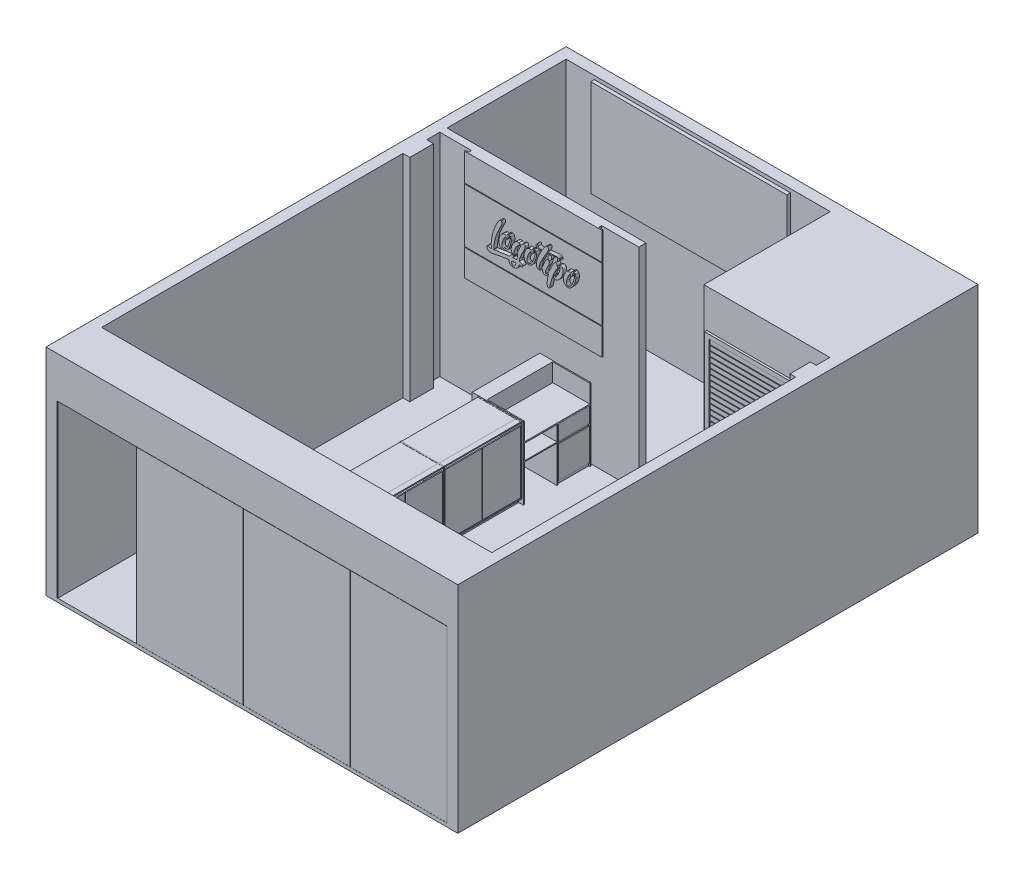
SolidWorks part; units mm, degrees
other "Cámara2"
other "Cámara3"
other "Cámara4"
other "Cámara5"
ref_plane "Alzado" through (0, 0, 0) normal (0, 0, 1) x (1, 0, 0)
ref_plane "Planta" through (0, 0, 0) normal (0, 1, 0) x (1, 0, 0)
ref_plane "Vista lateral" through (0, 0, 0) normal (1, 0, 0) x (0, 0, -1)
sketch "Croquis2" plane through (0, 0, 0) normal (0, 1, 0) x (1, 0, 0)
  line L0 (-7849.2928, -5615.0091) -> (-7999.2928, -5615.0091)
  line L1 (-7849.2928, 1434.9909) -> (-4194.2928, 1434.9909)
  line L2 (-7849.2928, 1434.9909) -> (-7849.2928, -495.0091)
  line L3 (-7849.2928, -825.0091) -> (-7849.2928, -5615.0091)
  line L4 (-2449.2928, -315.0091) -> (-2449.2928, -505.0091)
  line L5 (-2449.2928, -788.0091) -> (-2449.2928, -5615.0091)
  line L7 (-2449.2928, -315.0091) -> (-4194.2928, -315.0091)
  line L8 (-4194.2928, 1434.9909) -> (-4194.2928, -315.0091)
  line L9 (-2449.2928, -505.0091) -> (-2529.2928, -505.0091)
  line L11 (-2449.2928, -788.0091) -> (-2529.2928, -788.0091)
  line L12 (-2529.2928, -505.0091) -> (-2529.2928, -788.0091)
  line L13 (-7849.2928, -495.0091) -> (-7754.2928, -495.0091)
  line L15 (-7849.2928, -825.0091) -> (-7754.2928, -825.0091)
  line L16 (-7754.2928, -495.0091) -> (-7754.2928, -825.0091)
  line L17 (-2299.2928, -5615.0091) -> (-2449.2928, -5615.0091)
  line L18 (-2299.2928, -5615.0091) -> (-2299.2928, 1584.9909)
  line L19 (-2299.2928, 1584.9909) -> (-7999.2928, 1584.9909)
  line L20 (-7999.2928, -5615.0091) -> (-7999.2928, 1584.9909)
  dimension "D3" = 1750
  dimension "D4" = 1745
  dimension "D5" = 190
  dimension "D6" = 283
  dimension "D7" = 80
  dimension "D8" = 1930
  dimension "D9" = 330
  dimension "D10" = 95
  dimension "D11" = 150
  dimension "D12" = 150
  dimension "D13" = 150
extrude "Saliente-Extruir1" add sketch "Croquis2" along normal blind 2930
sketch "Croquis3" plane through (-2449.2928, 0, 0) normal (-1, 0, 0) x (0, 0, 1)
  line L0 (788.0091, 0) -> (5615.0091, 0) construction
  line L1 (5615.0091, 2930) -> (4995.0091, 2930)
  line L2 (5615.0091, 2930) -> (5615.0091, 2360)
  line L3 (5615.0091, 2360) -> (4995.0091, 2360)
  line L4 (4995.0091, 2930) -> (4995.0091, 2360)
  dimension "D1" = 620
  dimension "D2" = 2360
extrude "Saliente-Extruir2" add sketch "Croquis3" along normal blind 5461
sketch "Croquis4" plane through (0, 0, 4995.0091) normal (0, 0, -1) x (-1, 0, 0)
  line L0 (7849.2928, 2930) -> (2449.2928, 2930) construction
  line L1 (7649.2928, 2410) -> (7049.2928, 2410)
  line L2 (7649.2928, 2410) -> (7649.2928, 2830)
  line L3 (7649.2928, 2830) -> (7049.2928, 2830)
  line L4 (7049.2928, 2410) -> (7049.2928, 2830)
  line L5 (7849.2928, 2360) -> (2449.2928, 2360) construction
  line L6 (7849.2928, 2360) -> (7849.2928, 2930) construction
  line L7 (6159.2928, 2410) -> (6159.2928, 2830)
  line L8 (6759.2928, 2830) -> (6159.2928, 2830)
  line L9 (6759.2928, 2410) -> (6759.2928, 2830)
  line L10 (6759.2928, 2410) -> (6159.2928, 2410)
  line L11 (5269.2928, 2410) -> (5269.2928, 2830)
  line L12 (5869.2928, 2830) -> (5269.2928, 2830)
  line L13 (5869.2928, 2410) -> (5869.2928, 2830)
  line L14 (5869.2928, 2410) -> (5269.2928, 2410)
  line L15 (4379.2928, 2410) -> (4379.2928, 2830)
  line L16 (4979.2928, 2830) -> (4379.2928, 2830)
  line L17 (4979.2928, 2410) -> (4979.2928, 2830)
  line L18 (4979.2928, 2410) -> (4379.2928, 2410)
  line L19 (3489.2928, 2410) -> (3489.2928, 2830)
  line L20 (4089.2928, 2830) -> (3489.2928, 2830)
  line L21 (4089.2928, 2410) -> (4089.2928, 2830)
  line L22 (4089.2928, 2410) -> (3489.2928, 2410)
  line L23 (2599.2928, 2410) -> (2599.2928, 2830)
  line L24 (3199.2928, 2830) -> (2599.2928, 2830)
  line L25 (3199.2928, 2410) -> (3199.2928, 2830)
  line L26 (3199.2928, 2410) -> (2599.2928, 2410)
  dimension "D1" = 100
  dimension "D2" = 50
  dimension "D3" = 600
  dimension "D4" = 200
  dimension "D5" = 6
extrude "Cortar-Extruir1" cut sketch "Croquis4" against normal blind 500
sketch "Croquis5" plane through (0, 0, 0) normal (0, -1, 0) x (1, 0, 0)
  line L1 (-2299.2928, -1584.9909) -> (-7999.2928, -1584.9909)
  line L2 (-2299.2928, -1584.9909) -> (-2299.2928, 5615.0091)
  line L3 (-2299.2928, 5615.0091) -> (-7999.2928, 5615.0091)
  line L4 (-7999.2928, -1584.9909) -> (-7999.2928, 5615.0091)
extrude "Saliente-Extruir3" add sketch "Croquis5" along normal blind 50
sketch "Croquis6" plane through (0, 0, -1434.9909) normal (0, 0, 1) x (1, 0, 0)
  line L0 (-7999.2928, 2930) -> (-2299.2928, 2930) construction
  line L1 (-7409.2928, 2930) -> (-4694.2928, 2930)
  line L2 (-7409.2928, 2930) -> (-7409.2928, 1590)
  line L3 (-7409.2928, 1590) -> (-4694.2928, 1590)
  line L4 (-4694.2928, 2930) -> (-4694.2928, 1590)
  line L5 (-7849.2928, 2930) -> (-7849.2928, 0) construction
  line L6 (-7849.2928, 0) -> (-4194.2928, 0) construction
  line L7 (-4194.2928, 2930) -> (-4194.2928, 0) construction
  dimension "D1" = 440
  dimension "D2" = 1590
  dimension "D3" = 500
extrude "Saliente-Extruir4" add sketch "Croquis6" along normal blind 50 from offset 50 separate body
sketch "Croquis7" plane through (0, 0, 0) normal (0, 1, 0) x (1, 0, 0)
  line L0 (-7849.2928, -495.0091) -> (-7849.2928, 1434.9909) construction
  line L1 (-7849.2928, -315.0091) -> (-5094.2928, -315.0091)
  line L2 (-7849.2928, -315.0091) -> (-7849.2928, -215.0091)
  line L3 (-7849.2928, -215.0091) -> (-5094.2928, -215.0091)
  line L4 (-5094.2928, -315.0091) -> (-5094.2928, -215.0091)
  line L5 (-4194.2928, 1434.9909) -> (-4194.2928, -315.0091) construction
  dimension "D1" = 100
  dimension "D2" = 900
extrude "Saliente-Extruir5" add sketch "Croquis7" along normal up to vertex (2930 mm away) up to point (-7849.2928, 2930, 495.0091)
sketch "Croquis8" plane through (0, 0, 5615.0091) normal (0, 0, 1) x (1, 0, 0)
  line L0 (-7849.2928, 2930) -> (-7849.2928, 0) construction
  line L1 (-2451.2979, 1.2463) -> (-6749.2928, 1.2463)
  line L2 (-2451.2979, 1.2463) -> (-2451.2979, 2356.8001)
  line L3 (-2451.2979, 2356.8001) -> (-6749.2928, 2356.8001)
  line L4 (-6749.2928, 1.2463) -> (-6749.2928, 2356.8001)
  dimension "D1" = 1100
extrude "Saliente-Extruir6" add sketch "Croquis8" against normal blind 8 separate body
sketch "Croquis9" plane through (0, 0, 5615.0091) normal (0, 0, 1) x (1, 0, 0)
  line L0 (-2451.2979, 2356.8001) -> (-6749.2928, 2356.8001) construction
  line L1 (-5269.2928, 2356.8001) -> (-5264.2928, 2356.8001)
  line L2 (-5269.2928, 2356.8001) -> (-5269.2928, 0)
  line L3 (-5269.2928, 0) -> (-5264.2928, 0)
  line L4 (-5264.2928, 2356.8001) -> (-5264.2928, 0)
  line L5 (-2449.2928, 0) -> (-7849.2928, 0) construction
  line L6 (-3784.2928, 2356.8001) -> (-3784.2928, 0)
  line L7 (-3789.2928, 2356.8001) -> (-3789.2928, 0)
  line L8 (-3789.2928, 2356.8001) -> (-3784.2928, 2356.8001)
  line L9 (-3789.2928, 0) -> (-3784.2928, 0)
  line L10 (-6749.2928, 2356.8001) -> (-6749.2928, 1.2463) construction
  dimension "D1" = 5
  dimension "D3" = 1480
  dimension "D2" = 2
extrude "Cortar-Extruir2" cut sketch "Croquis9" against normal blind 8
sketch "Croquis11" plane through (0, 0, 0) normal (0, 1, 0) x (1, 0, 0)
  line L1 (-6273.8185, -5586.5744) -> (-5793.8185, -5586.5744)
  line L2 (-6273.8185, -5586.5744) -> (-6273.8185, -353.2208)
  line L3 (-6273.8185, -353.2208) -> (-5793.8185, -353.2208)
  line L4 (-5793.8185, -5586.5744) -> (-5793.8185, -353.2208)
  dimension "D1" = 5233.3536
  dimension "D2" = 480
extrude "Saliente-Extruir7" add sketch "Croquis11" along normal blind 70
sketch "Croquis12" plane through (0, 70, 0) normal (0, 1, 0) x (1, 0, 0)
  line L1 (-5744.5035, -5592.6591) -> (-6344.5035, -5592.6591)
  line L2 (-5744.5035, -5592.6591) -> (-5744.5035, -3442.6591)
  line L3 (-5744.5035, -3442.6591) -> (-6344.5035, -3442.6591)
  line L4 (-6344.5035, -5592.6591) -> (-6344.5035, -3442.6591)
  line L5 (-5744.5035, -3431.128) -> (-6344.5035, -3431.128)
  line L6 (-5744.5035, -3431.128) -> (-5744.5035, -1281.128)
  line L7 (-5744.5035, -1281.128) -> (-6344.5035, -1281.128)
  line L8 (-6344.5035, -3431.128) -> (-6344.5035, -1281.128)
  dimension "D1" = 600
  dimension "D2" = 2150
  dimension "D3" = 2150
extrude "Saliente-Extruir8" add sketch "Croquis12" along normal blind 930
sketch "Croquis13" plane through (0, 1000, 0) normal (0, 1, 0) x (1, 0, 0)
  line L0 (-6344.5035, -1281.128) -> (-6344.5035, -3431.128) construction
  line L1 (-6344.5035, -1296.128) -> (-5731.0709, -1296.128)
  line L2 (-6344.5035, -1296.128) -> (-6344.5035, -3416.128)
  line L3 (-6344.5035, -3416.128) -> (-5731.0709, -3416.128)
  line L4 (-5731.0709, -1296.128) -> (-5731.0709, -3416.128)
  line L5 (-6344.5035, -3442.6591) -> (-6344.5035, -5592.6591) construction
  line L6 (-6344.5035, -3457.6591) -> (-5731.0709, -3457.6591)
  line L7 (-6344.5035, -3457.6591) -> (-6344.5035, -5577.6591)
  line L8 (-6344.5035, -5577.6591) -> (-5731.0709, -5577.6591)
  line L9 (-5731.0709, -3457.6591) -> (-5731.0709, -5577.6591)
  line L10 (-6344.5035, -5592.6591) -> (-5744.5035, -5592.6591) construction
  line L11 (-5744.5035, -3442.6591) -> (-6344.5035, -3442.6591) construction
  line L12 (-6344.5035, -3431.128) -> (-5744.5035, -3431.128) construction
  line L13 (-5744.5035, -1281.128) -> (-6344.5035, -1281.128) construction
  dimension "D1" = 15
  dimension "D2" = 15
  dimension "D3" = 15
  dimension "D4" = 15
extrude "Cortar-Extruir3" cut sketch "Croquis13" against normal blind 915
sketch "Croquis14" plane through (0, 85, 0) normal (0, 1, 0) x (1, 0, 0)
  line L0 (-6344.5035, -1296.128) -> (-6344.5035, -3416.128) construction
  line L1 (-6344.5035, -2356.128) -> (-5744.5035, -2356.128)
  line L2 (-6344.5035, -2356.128) -> (-6344.5035, -2371.128)
  line L3 (-6344.5035, -2371.128) -> (-5744.5035, -2371.128)
  line L4 (-5744.5035, -2356.128) -> (-5744.5035, -2371.128)
  line L5 (-5744.5035, -3416.128) -> (-5744.5035, -1296.128) construction
  line L6 (-6344.5035, -3457.6591) -> (-6344.5035, -5577.6591) construction
  line L7 (-6344.5035, -4517.6591) -> (-5744.5035, -4517.6591)
  line L8 (-6344.5035, -4517.6591) -> (-6344.5035, -4532.6591)
  line L9 (-6344.5035, -4532.6591) -> (-5744.5035, -4532.6591)
  line L10 (-5744.5035, -4517.6591) -> (-5744.5035, -4532.6591)
  line L11 (-5744.5035, -5577.6591) -> (-5744.5035, -3457.6591) construction
  dimension "D1" = 15
  dimension "D2" = 15
extrude "Saliente-Extruir9" add sketch "Croquis14" along normal up to vertex (915 mm away) up to point (-5744.5035, 1000, 3431.128)
sketch "Croquis15" plane through (0, 85, 0) normal (0, 1, 0) x (1, 0, 0)
  line L0 (-5744.5035, -1296.128) -> (-6344.5035, -1296.128) construction
  line L1 (-6335.0437, -1296.128) -> (-6327.0437, -1296.128)
  line L2 (-6335.0437, -1296.128) -> (-6335.0437, -2356.128)
  line L3 (-6335.0437, -2356.128) -> (-6327.0437, -2356.128)
  line L4 (-6327.0437, -1296.128) -> (-6327.0437, -2356.128)
  line L5 (-5744.5035, -2356.128) -> (-6344.5035, -2356.128) construction
  line L6 (-6344.5035, -2371.128) -> (-5744.5035, -2371.128) construction
  line L7 (-6335.0437, -2371.128) -> (-6327.0437, -2371.128)
  line L8 (-6335.0437, -2371.128) -> (-6335.0437, -3416.128)
  line L9 (-6335.0437, -3416.128) -> (-6327.0437, -3416.128)
  line L10 (-6327.0437, -2371.128) -> (-6327.0437, -3416.128)
  line L11 (-6344.5035, -3416.128) -> (-5744.5035, -3416.128) construction
  line L13 (-5744.5035, -3457.6591) -> (-6344.5035, -3457.6591) construction
  line L14 (-6335.0437, -3457.6591) -> (-6327.0437, -3457.6591)
  line L15 (-6335.0437, -3457.6591) -> (-6335.0437, -5577.6591)
  line L16 (-6335.0437, -5577.6591) -> (-6327.0437, -5577.6591)
  line L17 (-6327.0437, -3457.6591) -> (-6327.0437, -5577.6591)
  line L18 (-6344.5035, -5577.6591) -> (-5744.5035, -5577.6591) construction
  dimension "D1" = 8
  dimension "D2" = 8
extrude "Saliente-Extruir10" add sketch "Croquis15" along normal blind 903
sketch "Croquis16" plane through (0, 70, 0) normal (0, 1, 0) x (1, 0, 0)
  line L1 (-6437.669, -341.0207) -> (-5730.993, -341.0207)
  line L2 (-6437.669, -341.0207) -> (-6437.669, -1277.1981)
  line L3 (-6437.669, -1277.1981) -> (-5730.993, -1277.1981)
  line L4 (-5730.993, -341.0207) -> (-5730.993, -1277.1981)
extrude "Saliente-Extruir11" add sketch "Croquis16" along normal up to vertex (930 mm away) and the other way up to vertex (70 mm away) up to point (-5744.5035, 1000, 1281.128) other way up to point (-6273.8185, 0, 353.2208)
sketch "Croquis17" plane through (-6437.669, 0, 0) normal (-1, 0, 0) x (0, 0, 1)
  line L0 (341.0207, 0) -> (1277.1981, 0) construction
  line L1 (1247.1981, 0) -> (371.0207, 0)
  line L2 (1247.1981, 0) -> (1247.1981, 970)
  line L3 (1247.1981, 970) -> (371.0207, 970)
  line L4 (371.0207, 0) -> (371.0207, 970)
  line L5 (341.0207, 1000) -> (1277.1981, 1000) construction
  line L6 (341.0207, 1000) -> (341.0207, 0) construction
  line L7 (1277.1981, 1000) -> (1277.1981, 0) construction
  dimension "D1" = 30
  dimension "D2" = 30
  dimension "D3" = 30
extrude "Cortar-Extruir4" cut sketch "Croquis17" against normal blind 155
sketch "Croquis18" plane through (-6282.669, 0, 0) normal (-1, 0, 0) x (0, 0, 1)
  line L0 (371.0207, 970) -> (371.0207, 0) construction
  line L1 (371.0207, 700.8111) -> (1247.1981, 700.8111)
  line L2 (371.0207, 700.8111) -> (371.0207, 690.8111)
  line L3 (371.0207, 690.8111) -> (1247.1981, 690.8111)
  line L4 (1247.1981, 700.8111) -> (1247.1981, 690.8111)
  line L5 (1247.1981, 0) -> (1247.1981, 970) construction
  line L7 (371.0207, 336.794) -> (1247.1981, 336.794)
  line L8 (371.0207, 336.794) -> (371.0207, 326.794)
  line L9 (371.0207, 326.794) -> (1247.1981, 326.794)
  line L10 (1247.1981, 336.794) -> (1247.1981, 326.794)
  dimension "D1" = 10
  dimension "D2" = 10
extrude "Cortar-Extruir5" cut sketch "Croquis18" against normal blind 155
sketch "Croquis19" plane through (0, 1000, 0) normal (0, 1, 0) x (1, 0, 0)
  line L0 (-5730.993, -1277.1981) -> (-5730.993, -341.0207) construction
  line L1 (-5730.993, -1262.1981) -> (-6244.9145, -1262.1981)
  line L2 (-5730.993, -1262.1981) -> (-5730.993, -356.0207)
  line L3 (-5730.993, -356.0207) -> (-6244.9145, -356.0207)
  line L4 (-6244.9145, -1262.1981) -> (-6244.9145, -356.0207)
  line L5 (-5730.993, -341.0207) -> (-6437.669, -341.0207) construction
  line L6 (-6437.669, -1277.1981) -> (-5730.993, -1277.1981) construction
  dimension "D1" = 15
  dimension "D2" = 15
extrude "Cortar-Extruir6" cut sketch "Croquis19" against normal blind 250
sketch "Croquis20" plane through (-5730.993, 0, 0) normal (1, 0, 0) x (0, 0, -1)
  line L1 (-1262.1981, 0) -> (-356.0207, 0)
  line L2 (-1262.1981, 0) -> (-1262.1981, 474.5874)
  line L3 (-809.1094, 474.5874) -> (-356.0207, 474.5874)
  line L4 (-356.0207, 0) -> (-356.0207, 474.5874)
  line L6 (-1262.1981, 474.5874) -> (-1262.1981, 731.9498)
  line L7 (-1262.1981, 731.9498) -> (-809.1094, 731.9498)
  line L8 (-809.1094, 474.5874) -> (-809.1094, 731.9498)
extrude "Cortar-Extruir7" cut sketch "Croquis20" against normal up to vertex (513.9215 mm away) up to point (-6244.9145, 750, 356.0207)
sketch "Croquis21" plane through (-6244.9145, 0, 0) normal (1, 0, 0) x (0, 0, -1)
  line L0 (-1262.1981, 0) -> (-356.0207, 0) construction
  line L1 (-809.1094, 474.5874) -> (-793.4637, 474.5874)
  line L2 (-809.1094, 474.5874) -> (-809.1094, 0)
  line L3 (-809.1094, 0) -> (-793.4637, 0)
  line L4 (-793.4637, 474.5874) -> (-793.4637, 0)
extrude "Saliente-Extruir12" add sketch "Croquis21" along normal up to vertex (513.9215 mm away) up to point (-5730.993, 474.5874, 356.0207)
sketch "Croquis22" plane through (-5730.993, 0, 0) normal (1, 0, 0) x (0, 0, -1)
  line L0 (-793.4637, 0) -> (-793.4637, 326.794) construction
  line L1 (-793.4637, 0) -> (-356.0207, 0)
  line L2 (-793.4637, 0) -> (-793.4637, 50)
  line L3 (-793.4637, 50) -> (-356.0207, 50)
  line L4 (-356.0207, 0) -> (-356.0207, 50)
  line L5 (-356.0207, 0) -> (-356.0207, 474.5874) construction
  dimension "D1" = 50
extrude "Saliente-Extruir13" add sketch "Croquis22" against normal blind 250 contours L3 L4 L1 L2
sketch "Croquis23" plane through (-5730.993, 0, 0) normal (1, 0, 0) x (0, 0, -1)
  line L1 (-793.4637, 474.5874) -> (-356.0207, 474.5874)
  line L2 (-793.4637, 474.5874) -> (-793.4637, 731.9498)
  line L3 (-793.4637, 731.9498) -> (-356.0207, 731.9498)
  line L4 (-356.0207, 474.5874) -> (-356.0207, 731.9498)
extrude "Cortar-Extruir8" cut sketch "Croquis23" against normal up to vertex (513.9215 mm away) up to point (-6244.9145, 336.794, 809.1094)
sketch "Croquis24" plane through (-5730.993, 0, 0) normal (1, 0, 0) x (0, 0, -1)
  line L0 (-809.1094, 0) -> (-341.0207, 0) construction
  line L1 (-793.4637, 50) -> (-356.0207, 50)
  line L2 (-793.4637, 50) -> (-793.4637, 0)
  line L3 (-793.4637, 0) -> (-356.0207, 0)
  line L4 (-356.0207, 50) -> (-356.0207, 0)
extrude "Cortar-Extruir9" cut sketch "Croquis24" against normal blind 18
sketch "Croquis25" plane through (-5748.993, 0, 0) normal (1, 0, 0) x (0, 0, -1)
  line L1 (-789.5623, 727.895) -> (-358.8959, 727.895)
  line L2 (-789.5623, 727.895) -> (-789.5623, 517.895)
  line L3 (-789.5623, 517.895) -> (-358.8959, 517.895)
  line L4 (-358.8959, 727.895) -> (-358.8959, 517.895)
  line L5 (-789.5623, 487.895) -> (-358.8959, 487.895)
  line L6 (-789.5623, 487.895) -> (-789.5623, 44.4055)
  line L7 (-789.5623, 44.4055) -> (-358.8959, 44.4055)
  line L8 (-358.8959, 487.895) -> (-358.8959, 44.4055)
  dimension "D1" = 210
  dimension "D2" = 30
extrude "Saliente-Extruir14" add sketch "Croquis25" against normal blind 98 and the other way blind 15
sketch "Croquis26" plane through (0, 0, 356.0207) normal (0, 0, 1) x (1, 0, 0)
  line L1 (-5790.7456, 525.0553) -> (-5748.3073, 525.0553)
  line L2 (-5790.7456, 525.0553) -> (-5790.7456, 485.704)
  line L3 (-5790.7456, 485.704) -> (-5748.3073, 485.704)
  line L4 (-5748.3073, 525.0553) -> (-5748.3073, 485.704)
extrude "Saliente-Extruir15" add sketch "Croquis26" along normal up to vertex (437.4431 mm away) up to point (-5730.993, 0, 793.4637)
sketch "Croquis27" plane through (-6244.9145, 0, 0) normal (1, 0, 0) x (0, 0, -1)
  line L0 (-1262.1981, 731.9498) -> (-1262.1981, 0) construction
  line L1 (-1262.1981, 522.4472) -> (-809.1094, 522.4472)
  line L2 (-1262.1981, 522.4472) -> (-1262.1981, 508.8133)
  line L3 (-1262.1981, 508.8133) -> (-809.1094, 508.8133)
  line L4 (-809.1094, 522.4472) -> (-809.1094, 508.8133)
  line L5 (-809.1094, 0) -> (-809.1094, 731.9498) construction
extrude "Saliente-Extruir16" add sketch "Croquis27" along normal up to vertex (513.9215 mm away) up to point (-5730.993, 0, 809.1094)
sketch "Croquis28" plane through (0, 0, 1296.128) normal (0, 0, 1) x (1, 0, 0)
  line L0 (-5744.5035, 1000) -> (-6344.5035, 1000) construction
  line L1 (-6319.4645, 700) -> (-5819.4645, 700)
  line L2 (-6319.4645, 700) -> (-6319.4645, 692)
  line L3 (-6319.4645, 692) -> (-5819.4645, 692)
  line L4 (-5819.4645, 700) -> (-5819.4645, 692)
  line L5 (-6319.4645, 392) -> (-5819.4645, 392)
  line L6 (-6319.4645, 400) -> (-5819.4645, 400)
  line L7 (-5819.4645, 400) -> (-5819.4645, 392)
  line L8 (-6319.4645, 400) -> (-6319.4645, 392)
  dimension "D1" = 500
  dimension "D2" = 8
  dimension "D3" = 300
  dimension "D4" = 2
extrude "Saliente-Extruir17" add sketch "Croquis28" along normal up to vertex (4281.531 mm away) up to point (-5744.5035, 1000, 5577.6591)
sketch "Croquis29" plane through (0, 0, 1296.128) normal (0, 0, 1) x (1, 0, 0)
  line L1 (-6340.7874, 997.831) -> (-5819.4645, 997.831)
  line L2 (-6340.7874, 997.831) -> (-6340.7874, 991.8705)
  line L3 (-6340.7874, 991.8705) -> (-5819.4645, 991.8705)
  line L4 (-5819.4645, 997.831) -> (-5819.4645, 991.8705)
extrude "Saliente-Extruir18" add sketch "Croquis29" along normal up to vertex (4296.531 mm away) up to point (-5744.5035, 1000, 5592.6591)
sketch "Croquis30" plane through (0, 0, 1296.128) normal (0, 0, 1) x (1, 0, 0)
  line L1 (-5818.52, 999.2539) -> (-5745.3813, 999.2539)
  line L2 (-5818.52, 999.2539) -> (-5818.52, 984.2539)
  line L3 (-5818.52, 984.2539) -> (-5745.3813, 984.2539)
  line L4 (-5745.3813, 999.2539) -> (-5745.3813, 984.2539)
  dimension "D1" = 15
extrude "Saliente-Extruir19" add sketch "Croquis30" along normal up to vertex (4281.531 mm away) up to point (-5744.5035, 1000, 5577.6591)
sketch "Croquis31" plane through (-5745.3813, 0, 0) normal (1, 0, 0) x (0, 0, -1)
  line L1 (-1300.1778, 949.2539) -> (-1829.1279, 949.2539)
  line L2 (-1300.1778, 949.2539) -> (-1300.1778, 90.4957)
  line L3 (-1300.1778, 90.4957) -> (-1829.1279, 90.4957)
  line L4 (-1829.1279, 949.2539) -> (-1829.1279, 90.4957)
  line L5 (-1834.8931, 90.4957) -> (-2346.9744, 90.4957)
  line L6 (-1834.8931, 90.4957) -> (-1834.8931, 949.2539)
  line L7 (-1834.8931, 949.2539) -> (-2346.9744, 949.2539)
  line L8 (-2346.9744, 90.4957) -> (-2346.9744, 949.2539)
  line L9 (-2356.128, 984.2539) -> (-1296.128, 984.2539) construction
  line L11 (-2379.7979, 949.2539) -> (-2893.6595, 949.2539)
  line L12 (-2379.7979, 949.2539) -> (-2379.7979, 90.4957)
  line L13 (-2379.7979, 90.4957) -> (-2893.6595, 90.4957)
  line L14 (-2893.6595, 949.2539) -> (-2893.6595, 90.4957)
  line L15 (-3407.9198, 949.2539) -> (-2899.0939, 949.2539)
  line L16 (-3407.9198, 949.2539) -> (-3407.9198, 90.4957)
  line L17 (-3407.9198, 90.4957) -> (-2899.0939, 90.4957)
  line L18 (-2899.0939, 949.2539) -> (-2899.0939, 90.4957)
  line L19 (-3462.3431, 949.2539) -> (-3982.1373, 949.2539)
  line L20 (-3462.3431, 949.2539) -> (-3462.3431, 90.4957)
  line L21 (-3462.3431, 90.4957) -> (-3982.1373, 90.4957)
  line L22 (-3982.1373, 949.2539) -> (-3982.1373, 90.4957)
  line L23 (-4511.3504, 949.3027) -> (-3992.1437, 949.3027)
  line L24 (-4511.3504, 949.3027) -> (-4511.3504, 90.4957)
  line L25 (-4511.3504, 90.4957) -> (-3992.1437, 90.4957)
  line L26 (-3992.1437, 949.3027) -> (-3992.1437, 90.4957)
  line L27 (-4537.0525, 949.3027) -> (-5054.5119, 949.3027)
  line L28 (-4537.0525, 949.3027) -> (-4537.0525, 90.4957)
  line L29 (-4537.0525, 90.4957) -> (-5054.5119, 90.4957)
  line L30 (-5054.5119, 949.3027) -> (-5054.5119, 90.4957)
  line L31 (-5573.1853, 949.3027) -> (-5058.2175, 949.3027)
  line L32 (-5573.1853, 949.3027) -> (-5573.1853, 90.4957)
  line L33 (-5573.1853, 90.4957) -> (-5058.2175, 90.4957)
  line L34 (-5058.2175, 949.3027) -> (-5058.2175, 90.4957)
  dimension "D1" = 35
  dimension "D2" = 35
extrude "Saliente-Extruir20" add sketch "Croquis31" against normal blind 15 separate body
sketch "Croquis32" plane through (0, 0, 0) normal (0, 1, 0) x (1, 0, 0)
  line L0 (-2449.2928, -5615.0091) -> (-7849.2928, -5615.0091) construction
  line L5 (-5362.7687, -4128.084) -> (-2962.7687, -4128.084)
  line L6 (-5362.7687, -4128.084) -> (-5362.7687, -4628.084)
  line L7 (-5362.7687, -4628.084) -> (-2962.7687, -4628.084)
  line L8 (-2962.7687, -4128.084) -> (-2962.7687, -4628.084)
  dimension "D1" = 1486.9252
  dimension "D2" = 2400
  dimension "D3" = 500
extrude "Saliente-Extruir21" add sketch "Croquis32" along normal blind 700
sketch "Croquis33" plane through (0, 0, 4628.084) normal (0, 0, 1) x (1, 0, 0)
  line L12 (-5320.7687, 42) -> (-3004.7687, 42)
  line L13 (-3004.7687, 42) -> (-3004.7687, 658)
  line L14 (-3004.7687, 658) -> (-5320.7687, 658)
  line L15 (-5320.7687, 658) -> (-5320.7687, 42)
  line L16 (-5320.7687, 42) -> (-3004.7687, 42)
  line L17 (-3004.7687, 42) -> (-3004.7687, 658)
  line L18 (-3004.7687, 658) -> (-5320.7687, 658)
  line L19 (-5320.7687, 658) -> (-5320.7687, 42)
  dimension "D1" = 42
extrude "Cortar-Extruir11" cut sketch "Croquis33" against normal up to vertex (500 mm away) up to point (-2962.7687, 700, 4128.084)
sketch "Croquis34" plane through (-5362.7687, 0, 0) normal (-1, 0, 0) x (0, 0, 1)
  line L8 (4170.084, 42) -> (4586.084, 42)
  line L9 (4586.084, 42) -> (4586.084, 658)
  line L10 (4586.084, 658) -> (4170.084, 658)
  line L11 (4170.084, 658) -> (4170.084, 42)
  line L12 (4170.084, 42) -> (4586.084, 42)
  line L13 (4586.084, 42) -> (4586.084, 658)
  line L14 (4586.084, 658) -> (4170.084, 658)
  line L15 (4170.084, 658) -> (4170.084, 42)
  dimension "D1" = 42
extrude "Cortar-Extruir12" cut sketch "Croquis34" against normal up to vertex (2400 mm away) up to point (-2962.7687, 700, 4128.084)
sketch "Croquis35" plane through (0, 42, 0) normal (0, 1, 0) x (1, 0, 0)
  line L1 (-3004.7687, -4586.084) -> (-5320.7687, -4586.084)
  line L2 (-3004.7687, -4586.084) -> (-3004.7687, -4170.084)
  line L3 (-3004.7687, -4170.084) -> (-5320.7687, -4170.084)
  line L4 (-5320.7687, -4586.084) -> (-5320.7687, -4170.084)
extrude "Cortar-Extruir13" cut sketch "Croquis35" against normal up to vertex (42 mm away) up to point (-5362.7687, 0, 4128.084)
sketch "Croquis36" plane through (0, 0, 4628.084) normal (0, 0, 1) x (1, 0, 0)
  line L0 (-5362.7687, 0) -> (-2962.7687, 0) construction
  line L1 (-3004.7687, 42) -> (-5320.7687, 42)
  line L2 (-3004.7687, 42) -> (-3004.7687, 0)
  line L3 (-3004.7687, 0) -> (-5320.7687, 0)
  line L4 (-5320.7687, 42) -> (-5320.7687, 0)
extrude "Cortar-Extruir14" cut sketch "Croquis36" against normal up to vertex (500 mm away) up to point (-3004.7687, 42, 4128.084)
sketch "Croquis37" plane through (0, 0, 4628.084) normal (0, 0, 1) x (1, 0, 0)
  line L0 (-4194.2928, 0) -> (-2449.2928, 0) construction
  line L1 (-4478.7472, 639.7339) -> (-3678.7472, 639.7339)
  line L2 (-4478.7472, 639.7339) -> (-4478.7472, 0)
  line L3 (-4478.7472, 0) -> (-3678.7472, 0)
  line L4 (-3678.7472, 639.7339) -> (-3678.7472, 0)
  dimension "D1" = 800
extrude "Saliente-Extruir22" add sketch "Croquis37" against normal blind 251 and the other way blind 180
sketch "Croquis38" plane through (0, 0, 4808.084) normal (0, 0, 1) x (1, 0, 0)
  line L1 (-4459.2142, 644.1817) -> (-3697.0645, 644.1817)
  line L2 (-4459.2142, 644.1817) -> (-4459.2142, 16.2765)
  line L3 (-4459.2142, 16.2765) -> (-3697.0645, 16.2765)
  line L4 (-3697.0645, 644.1817) -> (-3697.0645, 16.2765)
extrude "Cortar-Extruir15" cut sketch "Croquis38" against normal up to vertex (431 mm away) up to point (-3678.7472, 0, 4377.084)
sketch "Croquis39" plane through (0, 0, 4808.084) normal (0, 0, 1) x (1, 0, 0)
  line L1 (-4450.9926, 447.2858) -> (-3701.879, 447.2858)
  line L2 (-4450.9926, 447.2858) -> (-4450.9926, 439.2858)
  line L3 (-4450.9926, 439.2858) -> (-3701.879, 439.2858)
  line L4 (-3701.879, 447.2858) -> (-3701.879, 439.2858)
  line L5 (-4450.9926, 210.0986) -> (-3701.879, 210.0986)
  line L6 (-4450.9926, 210.0986) -> (-4450.9926, 202.0986)
  line L7 (-4450.9926, 202.0986) -> (-3701.879, 202.0986)
  line L8 (-3701.879, 210.0986) -> (-3701.879, 202.0986)
  dimension "D1" = 8
  dimension "D2" = 8
extrude "Saliente-Extruir23" add sketch "Croquis39" against normal up to vertex (431 mm away) separate body up to point (-4459.2142, 16.2765, 4377.084)
sketch "Croquis40" plane through (0, 0, 4628.084) normal (0, 0, 1) x (1, 0, 0)
  line L1 (-5362.0375, 701.643) -> (-2963.2437, 701.643)
  line L2 (-5362.0375, 701.643) -> (-5362.0375, 831.643)
  line L3 (-5362.0375, 831.643) -> (-2963.2437, 831.643)
  line L4 (-2963.2437, 701.643) -> (-2963.2437, 831.643)
  dimension "D1" = 130
extrude "Saliente-Extruir24" add sketch "Croquis40" against normal up to vertex (500 mm away) separate body up to point (-2962.7687, 700, 4128.084)
sketch "Croquis41" plane through (0, 0, 4628.084) normal (0, 0, 1) x (1, 0, 0)
  line L0 (-2963.2437, 831.643) -> (-5362.0375, 831.643) construction
  line L1 (-5347.0375, 831.643) -> (-2978.2437, 831.643)
  line L2 (-5347.0375, 831.643) -> (-5347.0375, 716.0432)
  line L3 (-5347.0375, 716.0432) -> (-2978.2437, 716.0432)
  line L4 (-2978.2437, 831.643) -> (-2978.2437, 716.0432)
  line L5 (-2963.2437, 701.643) -> (-2963.2437, 831.643) construction
  line L6 (-5362.0375, 831.643) -> (-5362.0375, 701.643) construction
  dimension "D1" = 15
  dimension "D2" = 15
extrude "Cortar-Extruir16" cut sketch "Croquis41" against normal blind 485
sketch "Croquis42" plane through (-2449.2928, 0, 0) normal (-1, 0, 0) x (0, 0, 1)
  line L0 (788.0091, 2930) -> (788.0091, 0) construction
  line L1 (1788.0091, 2401.1932) -> (788.0091, 2401.1932)
  line L2 (1788.0091, 2401.1932) -> (1788.0091, 1.1932)
  line L3 (1788.0091, 1.1932) -> (788.0091, 1.1932)
  line L4 (788.0091, 2401.1932) -> (788.0091, 1.1932)
  line L5 (2818.0091, 2401.1932) -> (2818.0091, 1.1932)
  line L6 (2818.0091, 2401.1932) -> (1818.0091, 2401.1932)
  line L7 (1818.0091, 2401.1932) -> (1818.0091, 1.1932)
  line L8 (2818.0091, 1.1932) -> (1818.0091, 1.1932)
  line L9 (3848.0091, 2401.1932) -> (3848.0091, 1.1932)
  line L10 (3848.0091, 2401.1932) -> (2848.0091, 2401.1932)
  line L11 (2848.0091, 2401.1932) -> (2848.0091, 1.1932)
  line L12 (3848.0091, 1.1932) -> (2848.0091, 1.1932)
  line L13 (4878.0091, 2401.1932) -> (4878.0091, 1.1932)
  line L14 (4878.0091, 2401.1932) -> (3878.0091, 2401.1932)
  line L15 (3878.0091, 2401.1932) -> (3878.0091, 1.1932)
  line L16 (4878.0091, 1.1932) -> (3878.0091, 1.1932)
  dimension "D1" = 1000
  dimension "D2" = 2400
  dimension "D3" = 4
extrude "Saliente-Extruir25" add sketch "Croquis42" along normal blind 15
sketch "Croquis43" plane through (-2464.2928, 0, 0) normal (-1, 0, 0) x (0, 0, 1)
  line L8 (4878.0091, 2401.1932) -> (3878.0091, 2401.1932)
  line L9 (3878.0091, 2401.1932) -> (3878.0091, 1.1932)
  line L10 (3878.0091, 1.1932) -> (4878.0091, 1.1932)
  line L11 (4878.0091, 1.1932) -> (4878.0091, 2401.1932)
  line L12 (4878.0091, 2401.1932) -> (3878.0091, 2401.1932)
  line L13 (3878.0091, 2401.1932) -> (3878.0091, 1.1932)
  line L14 (3878.0091, 1.1932) -> (4878.0091, 1.1932)
  line L15 (4878.0091, 1.1932) -> (4878.0091, 2401.1932)
  line L20 (2818.0091, 2401.1932) -> (1818.0091, 2401.1932)
  line L21 (1818.0091, 2401.1932) -> (1818.0091, 1.1932)
  line L22 (1818.0091, 1.1932) -> (2818.0091, 1.1932)
  line L23 (2818.0091, 1.1932) -> (2818.0091, 2401.1932)
  line L24 (2818.0091, 2401.1932) -> (1818.0091, 2401.1932)
  line L25 (1818.0091, 2401.1932) -> (1818.0091, 1.1932)
  line L26 (1818.0091, 1.1932) -> (2818.0091, 1.1932)
  line L27 (2818.0091, 1.1932) -> (2818.0091, 2401.1932)
  dimension "D1" = 0
  dimension "D2" = 0
extrude "Saliente-Extruir26" add sketch "Croquis43" along normal blind 365
sketch "Croquis44" plane through (-2829.2928, 0, 0) normal (-1, 0, 0) x (0, 0, 1)
  line L8 (4863.0091, 16.1932) -> (4863.0091, 2386.1932)
  line L9 (4863.0091, 2386.1932) -> (3893.0091, 2386.1932)
  line L10 (3893.0091, 2386.1932) -> (3893.0091, 16.1932)
  line L11 (3893.0091, 16.1932) -> (4863.0091, 16.1932)
  line L12 (4863.0091, 16.1932) -> (4863.0091, 2386.1932)
  line L13 (4863.0091, 2386.1932) -> (3893.0091, 2386.1932)
  line L14 (3893.0091, 2386.1932) -> (3893.0091, 16.1932)
  line L15 (3893.0091, 16.1932) -> (4863.0091, 16.1932)
  line L20 (2803.0091, 16.1932) -> (2803.0091, 2386.1932)
  line L21 (2803.0091, 2386.1932) -> (1833.0091, 2386.1932)
  line L22 (1833.0091, 2386.1932) -> (1833.0091, 16.1932)
  line L23 (1833.0091, 16.1932) -> (2803.0091, 16.1932)
  line L24 (2803.0091, 16.1932) -> (2803.0091, 2386.1932)
  line L25 (2803.0091, 2386.1932) -> (1833.0091, 2386.1932)
  line L26 (1833.0091, 2386.1932) -> (1833.0091, 16.1932)
  line L27 (1833.0091, 16.1932) -> (2803.0091, 16.1932)
  dimension "D1" = 15
  dimension "D2" = 15
extrude "Cortar-Extruir17" cut sketch "Croquis44" against normal up to vertex (380 mm away) up to point (-2449.2928, 2401.1932, 2818.0091)
sketch "Croquis45" plane through (-2449.2928, 0, 0) normal (-1, 0, 0) x (0, 0, 1)
  line L1 (4856.4501, 21.7147) -> (3896.8183, 21.7147)
  line L2 (4856.4501, 21.7147) -> (4856.4501, 371.7147)
  line L3 (4856.4501, 371.7147) -> (3896.8183, 371.7147)
  line L4 (3896.8183, 21.7147) -> (3896.8183, 371.7147)
  line L5 (2799.3583, 21.7147) -> (1836.9807, 21.7147)
  line L6 (2799.3583, 21.7147) -> (2799.3583, 371.7147)
  line L7 (2799.3583, 371.7147) -> (1836.9807, 371.7147)
  line L8 (1836.9807, 21.7147) -> (1836.9807, 371.7147)
  dimension "D1" = 350
  dimension "D2" = 350
extrude "Saliente-Extruir27" add sketch "Croquis45" along normal blind 365
sketch "Croquis46" plane through (-2814.2928, 0, 0) normal (-1, 0, 0) x (0, 0, 1)
  line L0 (1836.9807, 21.7147) -> (2799.3583, 21.7147) construction
  line L1 (1836.9807, 375.1203) -> (2318.1695, 375.1203)
  line L2 (1836.9807, 375.1203) -> (1836.9807, 21.7147)
  line L3 (1836.9807, 21.7147) -> (2318.1695, 21.7147)
  line L4 (2318.1695, 375.1203) -> (2318.1695, 21.7147)
  line L5 (3896.8183, 21.7147) -> (4856.4501, 21.7147) construction
  line L6 (2323.1695, 375.1203) -> (2799.3583, 375.1203)
  line L7 (2323.1695, 375.1203) -> (2323.1695, 21.7147)
  line L8 (2323.1695, 21.7147) -> (2799.3583, 21.7147)
  line L9 (2799.3583, 375.1203) -> (2799.3583, 21.7147)
  line L10 (3896.6897, 375.1203) -> (4376.6342, 375.1203)
  line L11 (3896.6897, 375.1203) -> (3896.6897, 21.7147)
  line L12 (3896.6897, 21.7147) -> (4376.6342, 21.7147)
  line L13 (4376.6342, 375.1203) -> (4376.6342, 21.7147)
  line L15 (4381.6342, 375.1203) -> (4856.4501, 375.1203)
  line L16 (4381.6342, 375.1203) -> (4381.6342, 21.7147)
  line L17 (4381.6342, 21.7147) -> (4856.4501, 21.7147)
  line L18 (4856.4501, 375.1203) -> (4856.4501, 21.7147)
  dimension "D1" = 5
  dimension "D2" = 5
extrude "Saliente-Extruir28" add sketch "Croquis46" along normal blind 15
sketch "Croquis47" plane through (-2464.2928, 0, 0) normal (-1, 0, 0) x (0, 0, 1)
  line L0 (2848.0091, 2401.1932) -> (2848.0091, 1.1932) construction
  line L1 (2848.0091, 2001.1932) -> (3848.0091, 2001.1932)
  line L2 (2848.0091, 2001.1932) -> (2848.0091, 1986.1932)
  line L3 (2848.0091, 1986.1932) -> (3848.0091, 1986.1932)
  line L4 (3848.0091, 2001.1932) -> (3848.0091, 1986.1932)
  line L5 (3848.0091, 1.1932) -> (3848.0091, 2401.1932) construction
  line L6 (3848.0091, 2401.1932) -> (2848.0091, 2401.1932) construction
  line L7 (2848.0091, 1586.1932) -> (3848.0091, 1586.1932)
  line L8 (2848.0091, 1601.1932) -> (3848.0091, 1601.1932)
  line L9 (3848.0091, 1601.1932) -> (3848.0091, 1586.1932)
  line L10 (2848.0091, 1601.1932) -> (2848.0091, 1586.1932)
  line L11 (2848.0091, 1186.1932) -> (3848.0091, 1186.1932)
  line L12 (2848.0091, 1201.1932) -> (3848.0091, 1201.1932)
  line L13 (3848.0091, 1201.1932) -> (3848.0091, 1186.1932)
  line L14 (2848.0091, 1201.1932) -> (2848.0091, 1186.1932)
  line L15 (2848.0091, 786.1932) -> (3848.0091, 786.1932)
  line L16 (2848.0091, 801.1932) -> (3848.0091, 801.1932)
  line L17 (3848.0091, 801.1932) -> (3848.0091, 786.1932)
  line L18 (2848.0091, 801.1932) -> (2848.0091, 786.1932)
  line L19 (2848.0091, 386.1932) -> (3848.0091, 386.1932)
  line L20 (2848.0091, 401.1932) -> (3848.0091, 401.1932)
  line L21 (3848.0091, 401.1932) -> (3848.0091, 386.1932)
  line L22 (2848.0091, 401.1932) -> (2848.0091, 386.1932)
  line L23 (788.0091, 1986.1932) -> (1788.0091, 1986.1932)
  line L24 (788.0091, 2001.1932) -> (1788.0091, 2001.1932)
  line L25 (1788.0091, 2001.1932) -> (1788.0091, 1986.1932)
  line L26 (788.0091, 2001.1932) -> (788.0091, 1986.1932)
  line L27 (788.0091, 1601.1932) -> (1788.0091, 1601.1932)
  line L28 (788.0091, 1586.1932) -> (1788.0091, 1586.1932)
  line L29 (1788.0091, 1601.1932) -> (1788.0091, 1586.1932)
  line L30 (788.0091, 1601.1932) -> (788.0091, 1586.1932)
  line L31 (788.0091, 1186.1932) -> (1788.0091, 1186.1932)
  line L32 (788.0091, 1201.1932) -> (1788.0091, 1201.1932)
  line L33 (788.0091, 1201.1932) -> (788.0091, 1186.1932)
  line L34 (1788.0091, 1201.1932) -> (1788.0091, 1186.1932)
  line L35 (1788.0091, 801.1932) -> (1788.0091, 786.1932)
  line L36 (788.0091, 786.1932) -> (1788.0091, 786.1932)
  line L37 (788.0091, 801.1932) -> (1788.0091, 801.1932)
  line L38 (788.0091, 801.1932) -> (788.0091, 786.1932)
  line L39 (788.0091, 386.1932) -> (1788.0091, 386.1932)
  line L40 (788.0091, 401.1932) -> (1788.0091, 401.1932)
  line L41 (788.0091, 401.1932) -> (788.0091, 386.1932)
  line L42 (1788.0091, 401.1932) -> (1788.0091, 386.1932)
  dimension "D1" = 15
  dimension "D2" = 400
  dimension "D3" = 5
  dimension "D4" = 2
extrude "Saliente-Extruir29" add sketch "Croquis47" along normal blind 280
sketch "Croquis48" plane through (-2449.2928, 0, 0) normal (-1, 0, 0) x (0, 0, 1)
  line L0 (2803.0091, 16.1932) -> (2803.0091, 2386.1932) construction
  line L1 (2803.0091, 1986.1932) -> (1833.0091, 1986.1932)
  line L2 (2803.0091, 1986.1932) -> (2803.0091, 2001.1932)
  line L3 (2803.0091, 2001.1932) -> (1833.0091, 2001.1932)
  line L4 (1833.0091, 1986.1932) -> (1833.0091, 2001.1932)
  line L5 (1833.0091, 2386.1932) -> (1833.0091, 16.1932) construction
  line L6 (2803.0091, 1586.1932) -> (2803.0091, 1601.1932)
  line L7 (2803.0091, 1586.1932) -> (1833.0091, 1586.1932)
  line L8 (1833.0091, 1586.1932) -> (1833.0091, 1601.1932)
  line L9 (2803.0091, 1601.1932) -> (1833.0091, 1601.1932)
  line L10 (2803.0091, 1186.1932) -> (2803.0091, 1201.1932)
  line L11 (2803.0091, 1186.1932) -> (1833.0091, 1186.1932)
  line L12 (1833.0091, 1186.1932) -> (1833.0091, 1201.1932)
  line L13 (2803.0091, 1201.1932) -> (1833.0091, 1201.1932)
  line L14 (2803.0091, 786.1932) -> (2803.0091, 801.1932)
  line L15 (2803.0091, 786.1932) -> (1833.0091, 786.1932)
  line L16 (1833.0091, 786.1932) -> (1833.0091, 801.1932)
  line L17 (2803.0091, 801.1932) -> (1833.0091, 801.1932)
  line L18 (3893.0091, 2386.1932) -> (3893.0091, 16.1932) construction
  line L19 (3893.0091, 2001.1932) -> (4863.0091, 2001.1932)
  line L20 (3893.0091, 2001.1932) -> (3893.0091, 1986.1932)
  line L21 (3893.0091, 1986.1932) -> (4863.0091, 1986.1932)
  line L22 (4863.0091, 2001.1932) -> (4863.0091, 1986.1932)
  line L23 (4863.0091, 16.1932) -> (4863.0091, 2386.1932) construction
  line L24 (3893.0091, 1601.1932) -> (3893.0091, 1586.1932)
  line L25 (3893.0091, 1601.1932) -> (4863.0091, 1601.1932)
  line L26 (4863.0091, 1601.1932) -> (4863.0091, 1586.1932)
  line L27 (3893.0091, 1586.1932) -> (4863.0091, 1586.1932)
  line L28 (3893.0091, 1201.1932) -> (3893.0091, 1186.1932)
  line L29 (3893.0091, 1201.1932) -> (4863.0091, 1201.1932)
  line L30 (4863.0091, 1201.1932) -> (4863.0091, 1186.1932)
  line L31 (3893.0091, 1186.1932) -> (4863.0091, 1186.1932)
  line L32 (3893.0091, 801.1932) -> (3893.0091, 786.1932)
  line L33 (3893.0091, 801.1932) -> (4863.0091, 801.1932)
  line L34 (4863.0091, 801.1932) -> (4863.0091, 786.1932)
  line L35 (3893.0091, 786.1932) -> (4863.0091, 786.1932)
  dimension "D1" = 4
  dimension "D2" = 4
extrude "Saliente-Extruir30" add sketch "Croquis48" along normal blind 370
sketch "Croquis49" plane through (-2464.2928, 0, 0) normal (-1, 0, 0) x (0, 0, 1)
  line L1 (2848.0091, 2401.1932) -> (3848.0091, 2401.1932)
  line L2 (2848.0091, 2401.1932) -> (2848.0091, 1986.1932)
  line L3 (2848.0091, 1986.1932) -> (3848.0091, 1986.1932)
  line L4 (3848.0091, 2401.1932) -> (3848.0091, 1986.1932)
  line L5 (788.0091, 2401.1932) -> (1788.0091, 2401.1932)
  line L6 (788.0091, 2401.1932) -> (788.0091, 1986.1932)
  line L7 (788.0091, 1986.1932) -> (1788.0091, 1986.1932)
  line L8 (1788.0091, 2401.1932) -> (1788.0091, 1986.1932)
extrude "Saliente-Extruir31" add sketch "Croquis49" along normal up to vertex (280 mm away) up to point (-2744.2928, 2001.1932, 1788.0091)
sketch "Croquis50" plane through (0, 2401.1932, 0) normal (0, 1, 0) x (1, 0, 0)
  line L1 (-2745.598, -788.0091) -> (-2760.598, -788.0091)
  line L2 (-2745.598, -788.0091) -> (-2745.598, -1788.0091)
  line L3 (-2745.598, -1788.0091) -> (-2760.598, -1788.0091)
  line L4 (-2760.598, -788.0091) -> (-2760.598, -1788.0091)
  line L5 (-2760.598, -2848.0091) -> (-2744.6541, -2848.0091)
  line L6 (-2760.598, -2848.0091) -> (-2760.598, -3848.0091)
  line L7 (-2760.598, -3848.0091) -> (-2744.6541, -3848.0091)
  line L8 (-2744.6541, -2848.0091) -> (-2744.6541, -3848.0091)
  dimension "D1" = 15
extrude "Saliente-Extruir32" add sketch "Croquis50" against normal up to vertex (415 mm away) separate body up to point (-2744.2928, 1986.1932, 2848.0091)
sketch "Croquis52" plane through (-2464.2928, 0, 0) normal (-1, 0, 0) x (0, 0, 1)
  line L0 (3848.0091, 1201.1932) -> (3848.0091, 1586.1932) construction
  line L1 (2848.0091, 2401.1932) -> (2848.0091, 1.1932) construction
  circle A0 centre (3748.0091, 1573.9118) radius 12.5
  circle A1 centre (2948.0091, 1573.9118) radius 12.5
  circle A2 centre (2948.0091, 1173.9118) radius 12.5
  circle A3 centre (3748.0091, 1173.9118) radius 12.5
  circle A4 centre (2948.0091, 773.9118) radius 12.5
  circle A5 centre (3748.0091, 773.9118) radius 12.5
  circle A6 centre (2948.0091, 373.9118) radius 12.5
  circle A7 centre (3748.0091, 373.9118) radius 12.5
  circle A8 centre (888.0091, 1573.9118) radius 12.5
  circle A9 centre (1688.0091, 1573.9118) radius 12.5
  circle A10 centre (1688.0091, 1173.9118) radius 12.5
  circle A11 centre (1688.0091, 773.9118) radius 12.5
  circle A12 centre (1688.0091, 373.9118) radius 12.5
  circle A13 centre (888.0091, 373.9118) radius 12.5
  circle A14 centre (888.0091, 773.9118) radius 12.5
  circle A15 centre (888.0091, 1173.9118) radius 12.5
  dimension "D1" = 25
  dimension "D3" = 25
  dimension "D2" = 100
  dimension "D4" = 100
  dimension "D5" = 4
  dimension "D6" = 2
extrude "Saliente-Extruir33" add sketch "Croquis52" along normal blind 40
sketch "Croquis53" plane through (-2449.2928, 0, 0) normal (-1, 0, 0) x (0, 0, 1)
  line L0 (4878.0091, 1.1932) -> (4878.0091, 2401.1932) construction
  line L1 (4878.0091, 1141.4752) -> (5549.3907, 1141.4752)
  line L2 (4878.0091, 1141.4752) -> (4878.0091, 1111.4752)
  line L3 (4878.0091, 1111.4752) -> (5549.3907, 1111.4752)
  line L4 (5549.3907, 1141.4752) -> (5549.3907, 1111.4752)
  line L6 (4878.0091, 1552.8915) -> (5549.3907, 1552.8915)
  line L7 (4878.0091, 1552.8915) -> (4878.0091, 1522.8915)
  line L8 (4878.0091, 1522.8915) -> (5549.3907, 1522.8915)
  line L9 (5549.3907, 1552.8915) -> (5549.3907, 1522.8915)
  line L10 (4878.0091, 1937.7425) -> (5549.3907, 1937.7425)
  line L11 (4878.0091, 1937.7425) -> (4878.0091, 1907.7425)
  line L12 (4878.0091, 1907.7425) -> (5549.3907, 1907.7425)
  line L13 (5549.3907, 1937.7425) -> (5549.3907, 1907.7425)
  dimension "D1" = 30
  dimension "D2" = 30
  dimension "D3" = 30
extrude "Saliente-Extruir34" add sketch "Croquis53" along normal blind 280
sketch "Croquis54" plane through (-2449.2928, 0, 0) normal (-1, 0, 0) x (0, 0, 1)
  circle A0 centre (5488.2516, 1895.356) radius 12.5
  circle A1 centre (5488.2516, 1510.2569) radius 12.5
  circle A2 centre (5488.2516, 1098.6055) radius 12.5
  dimension "D1" = 25
  dimension "D2" = 25
  dimension "D3" = 25
extrude "Saliente-Extruir35" add sketch "Croquis54" along normal blind 50
sketch "Croquis55" plane through (0, 0, 315.0091) normal (0, 0, 1) x (1, 0, 0)
  line L1 (-4153.3473, 2401.1932) -> (-2565.0985, 2401.1932)
  line L2 (-4153.3473, 2401.1932) -> (-4153.3473, 398.8813)
  line L3 (-4153.3473, 398.8813) -> (-2565.0985, 398.8813)
  line L4 (-2565.0985, 2401.1932) -> (-2565.0985, 398.8813)
extrude "Saliente-Extruir36" add sketch "Croquis55" along normal blind 15
sketch "Croquis56" plane through (0, 0, 315.0091) normal (0, 0, 1) x (1, 0, 0)
  line L0 (-4194.2928, 0) -> (-2449.2928, 0) construction
  line L1 (-4149.2642, 0) -> (-2565.0985, 0)
  line L2 (-4149.2642, 0) -> (-4149.2642, 398.0393)
  line L3 (-4149.2642, 398.0393) -> (-2565.0985, 398.0393)
  line L4 (-2565.0985, 0) -> (-2565.0985, 398.0393)
extrude "Saliente-Extruir37" add sketch "Croquis56" along normal blind 350
sketch "Croquis57" plane through (0, 0, 665.0091) normal (0, 0, 1) x (1, 0, 0)
  line L8 (-4134.2642, 383.0393) -> (-4134.2642, 15)
  line L9 (-4134.2642, 15) -> (-2580.0985, 15)
  line L10 (-2580.0985, 15) -> (-2580.0985, 383.0393)
  line L11 (-2580.0985, 383.0393) -> (-4134.2642, 383.0393)
  line L12 (-4134.2642, 383.0393) -> (-4134.2642, 15)
  line L13 (-4134.2642, 15) -> (-2580.0985, 15)
  line L14 (-2580.0985, 15) -> (-2580.0985, 383.0393)
  line L15 (-2580.0985, 383.0393) -> (-4134.2642, 383.0393)
  dimension "D1" = 15
extrude "Cortar-Extruir18" cut sketch "Croquis57" against normal blind 350
sketch "Croquis58" plane through (0, 0, 315.0091) normal (0, 0, 1) x (1, 0, 0)
  line L0 (-2580.0985, 383.0393) -> (-4134.2642, 383.0393) construction
  line L1 (-3357.1814, 383.0393) -> (-3342.1814, 383.0393)
  line L2 (-3357.1814, 383.0393) -> (-3357.1814, 15)
  line L3 (-3357.1814, 15) -> (-3342.1814, 15)
  line L4 (-3342.1814, 383.0393) -> (-3342.1814, 15)
  line L5 (-4134.2642, 15) -> (-2580.0985, 15) construction
  dimension "D1" = 15
extrude "Saliente-Extruir38" add sketch "Croquis58" along normal blind 335
sketch "Croquis59" plane through (0, 0, 650.0091) normal (0, 0, 1) x (1, 0, 0)
  line L1 (-3352.2742, 342.5044) -> (-4132.6817, 342.5044)
  line L2 (-3352.2742, 342.5044) -> (-3352.2742, 16.5576)
  line L3 (-3352.2742, 16.5576) -> (-4132.6817, 16.5576)
  line L4 (-4132.6817, 342.5044) -> (-4132.6817, 16.5576)
  line L5 (-3345.9022, 342.5044) -> (-2580.2379, 342.5044)
  line L6 (-3345.9022, 342.5044) -> (-3345.9022, 16.5576)
  line L7 (-3345.9022, 16.5576) -> (-2580.2379, 16.5576)
  line L8 (-2580.2379, 342.5044) -> (-2580.2379, 16.5576)
extrude "Saliente-Extruir39" add sketch "Croquis59" along normal blind 14
sketch "Croquis60" plane through (-4149.2642, 0, 0) normal (-1, 0, 0) x (0, 0, 1)
  line L0 (315.0091, 383.0393) -> (665.0091, 383.0393) construction
  line L1 (636.171, 383.0393) -> (621.0023, 383.0393)
  line L2 (636.171, 383.0393) -> (636.171, 313.0393)
  line L3 (636.171, 313.0393) -> (621.0023, 313.0393)
  line L4 (621.0023, 383.0393) -> (621.0023, 313.0393)
  dimension "D1" = 70
extrude "Saliente-Extruir40" add sketch "Croquis60" against normal blind 1581
sketch "Croquis61" plane through (0, 0, 330.0091) normal (0, 0, 1) x (1, 0, 0)
  line L8 (-4093.3473, 2341.1932) -> (-4093.3473, 458.8813)
  line L9 (-4093.3473, 458.8813) -> (-2625.0985, 458.8813)
  line L10 (-2625.0985, 458.8813) -> (-2625.0985, 2341.1932)
  line L11 (-2625.0985, 2341.1932) -> (-4093.3473, 2341.1932)
  line L12 (-4093.3473, 2341.1932) -> (-4093.3473, 458.8813)
  line L13 (-4093.3473, 458.8813) -> (-2625.0985, 458.8813)
  line L14 (-2625.0985, 458.8813) -> (-2625.0985, 2341.1932)
  line L15 (-2625.0985, 2341.1932) -> (-4093.3473, 2341.1932)
  line L20 (-4153.3473, 2401.1932) -> (-4153.3473, 398.8813)
  line L21 (-4153.3473, 398.8813) -> (-2565.0985, 398.8813)
  line L22 (-2565.0985, 398.8813) -> (-2565.0985, 2401.1932)
  line L23 (-2565.0985, 2401.1932) -> (-4153.3473, 2401.1932)
  line L24 (-4153.3473, 2401.1932) -> (-4153.3473, 398.8813)
  line L25 (-4153.3473, 398.8813) -> (-2565.0985, 398.8813)
  line L26 (-2565.0985, 398.8813) -> (-2565.0985, 2401.1932)
  line L27 (-2565.0985, 2401.1932) -> (-4153.3473, 2401.1932)
  dimension "D1" = 60
  dimension "D2" = 0
extrude "Saliente-Extruir41" add sketch "Croquis61" along normal blind 15
sketch "Croquis62" plane through (0, 0, 330.0091) normal (0, 0, 1) x (1, 0, 0)
  line L0 (-4093.3473, 2341.1932) -> (-4093.3473, 458.8813) construction
  line L1 (-4093.3473, 2271.1932) -> (-2625.0985, 2271.1932)
  line L2 (-4093.3473, 2271.1932) -> (-4093.3473, 2259.1932)
  line L3 (-4093.3473, 2259.1932) -> (-2625.0985, 2259.1932)
  line L4 (-2625.0985, 2271.1932) -> (-2625.0985, 2259.1932)
  line L5 (-2625.0985, 458.8813) -> (-2625.0985, 2341.1932) construction
  line L6 (-2625.0985, 2341.1932) -> (-4093.3473, 2341.1932) construction
  line L7 (-4093.3473, 2189.1932) -> (-2625.0985, 2189.1932)
  line L8 (-4093.3473, 2201.1932) -> (-2625.0985, 2201.1932)
  line L9 (-2625.0985, 2201.1932) -> (-2625.0985, 2189.1932)
  line L10 (-4093.3473, 2201.1932) -> (-4093.3473, 2189.1932)
  line L11 (-4093.3473, 2119.1932) -> (-2625.0985, 2119.1932)
  line L12 (-4093.3473, 2131.1932) -> (-2625.0985, 2131.1932)
  line L13 (-2625.0985, 2131.1932) -> (-2625.0985, 2119.1932)
  line L14 (-4093.3473, 2131.1932) -> (-4093.3473, 2119.1932)
  line L15 (-4093.3473, 2049.1932) -> (-2625.0985, 2049.1932)
  line L16 (-4093.3473, 2061.1932) -> (-2625.0985, 2061.1932)
  line L17 (-2625.0985, 2061.1932) -> (-2625.0985, 2049.1932)
  line L18 (-4093.3473, 2061.1932) -> (-4093.3473, 2049.1932)
  line L19 (-4093.3473, 1979.1932) -> (-2625.0985, 1979.1932)
  line L20 (-4093.3473, 1991.1932) -> (-2625.0985, 1991.1932)
  line L21 (-2625.0985, 1991.1932) -> (-2625.0985, 1979.1932)
  line L22 (-4093.3473, 1991.1932) -> (-4093.3473, 1979.1932)
  line L23 (-4093.3473, 1909.1932) -> (-2625.0985, 1909.1932)
  line L24 (-4093.3473, 1921.1932) -> (-2625.0985, 1921.1932)
  line L25 (-2625.0985, 1921.1932) -> (-2625.0985, 1909.1932)
  line L26 (-4093.3473, 1921.1932) -> (-4093.3473, 1909.1932)
  line L27 (-4093.3473, 1839.1932) -> (-2625.0985, 1839.1932)
  line L28 (-4093.3473, 1851.1932) -> (-2625.0985, 1851.1932)
  line L29 (-2625.0985, 1851.1932) -> (-2625.0985, 1839.1932)
  line L30 (-4093.3473, 1851.1932) -> (-4093.3473, 1839.1932)
  line L31 (-4093.3473, 1769.1932) -> (-2625.0985, 1769.1932)
  line L32 (-4093.3473, 1781.1932) -> (-2625.0985, 1781.1932)
  line L33 (-2625.0985, 1781.1932) -> (-2625.0985, 1769.1932)
  line L34 (-4093.3473, 1781.1932) -> (-4093.3473, 1769.1932)
  line L35 (-4093.3473, 1699.1932) -> (-2625.0985, 1699.1932)
  line L36 (-4093.3473, 1711.1932) -> (-2625.0985, 1711.1932)
  line L37 (-2625.0985, 1711.1932) -> (-2625.0985, 1699.1932)
  line L38 (-4093.3473, 1711.1932) -> (-4093.3473, 1699.1932)
  line L39 (-4093.3473, 1629.1932) -> (-2625.0985, 1629.1932)
  line L40 (-4093.3473, 1641.1932) -> (-2625.0985, 1641.1932)
  line L41 (-2625.0985, 1641.1932) -> (-2625.0985, 1629.1932)
  line L42 (-4093.3473, 1641.1932) -> (-4093.3473, 1629.1932)
  line L43 (-4093.3473, 1559.1932) -> (-2625.0985, 1559.1932)
  line L44 (-4093.3473, 1571.1932) -> (-2625.0985, 1571.1932)
  line L45 (-2625.0985, 1571.1932) -> (-2625.0985, 1559.1932)
  line L46 (-4093.3473, 1571.1932) -> (-4093.3473, 1559.1932)
  line L47 (-4093.3473, 1489.1932) -> (-2625.0985, 1489.1932)
  line L48 (-4093.3473, 1501.1932) -> (-2625.0985, 1501.1932)
  line L49 (-2625.0985, 1501.1932) -> (-2625.0985, 1489.1932)
  line L50 (-4093.3473, 1501.1932) -> (-4093.3473, 1489.1932)
  line L51 (-4093.3473, 1419.1932) -> (-2625.0985, 1419.1932)
  line L52 (-4093.3473, 1431.1932) -> (-2625.0985, 1431.1932)
  line L53 (-2625.0985, 1431.1932) -> (-2625.0985, 1419.1932)
  line L54 (-4093.3473, 1431.1932) -> (-4093.3473, 1419.1932)
  line L55 (-4093.3473, 1349.1932) -> (-2625.0985, 1349.1932)
  line L56 (-4093.3473, 1361.1932) -> (-2625.0985, 1361.1932)
  line L57 (-2625.0985, 1361.1932) -> (-2625.0985, 1349.1932)
  line L58 (-4093.3473, 1361.1932) -> (-4093.3473, 1349.1932)
  line L59 (-4093.3473, 1279.1932) -> (-2625.0985, 1279.1932)
  line L60 (-4093.3473, 1291.1932) -> (-2625.0985, 1291.1932)
  line L61 (-2625.0985, 1291.1932) -> (-2625.0985, 1279.1932)
  line L62 (-4093.3473, 1291.1932) -> (-4093.3473, 1279.1932)
  line L63 (-4093.3473, 1209.1932) -> (-2625.0985, 1209.1932)
  line L64 (-4093.3473, 1221.1932) -> (-2625.0985, 1221.1932)
  line L65 (-2625.0985, 1221.1932) -> (-2625.0985, 1209.1932)
  line L66 (-4093.3473, 1221.1932) -> (-4093.3473, 1209.1932)
  line L67 (-4093.3473, 1139.1932) -> (-2625.0985, 1139.1932)
  line L68 (-4093.3473, 1151.1932) -> (-2625.0985, 1151.1932)
  line L69 (-2625.0985, 1151.1932) -> (-2625.0985, 1139.1932)
  line L70 (-4093.3473, 1151.1932) -> (-4093.3473, 1139.1932)
  line L71 (-4093.3473, 1069.1932) -> (-2625.0985, 1069.1932)
  line L72 (-4093.3473, 1081.1932) -> (-2625.0985, 1081.1932)
  line L73 (-2625.0985, 1081.1932) -> (-2625.0985, 1069.1932)
  line L74 (-4093.3473, 1081.1932) -> (-4093.3473, 1069.1932)
  line L75 (-4093.3473, 999.1932) -> (-2625.0985, 999.1932)
  line L76 (-4093.3473, 1011.1932) -> (-2625.0985, 1011.1932)
  line L77 (-2625.0985, 1011.1932) -> (-2625.0985, 999.1932)
  line L78 (-4093.3473, 1011.1932) -> (-4093.3473, 999.1932)
  line L79 (-4093.3473, 929.1932) -> (-2625.0985, 929.1932)
  line L80 (-4093.3473, 941.1932) -> (-2625.0985, 941.1932)
  line L81 (-2625.0985, 941.1932) -> (-2625.0985, 929.1932)
  line L82 (-4093.3473, 941.1932) -> (-4093.3473, 929.1932)
  line L83 (-4093.3473, 859.1932) -> (-2625.0985, 859.1932)
  line L84 (-4093.3473, 871.1932) -> (-2625.0985, 871.1932)
  line L85 (-2625.0985, 871.1932) -> (-2625.0985, 859.1932)
  line L86 (-4093.3473, 871.1932) -> (-4093.3473, 859.1932)
  line L87 (-4093.3473, 789.1932) -> (-2625.0985, 789.1932)
  line L88 (-4093.3473, 801.1932) -> (-2625.0985, 801.1932)
  line L89 (-2625.0985, 801.1932) -> (-2625.0985, 789.1932)
  line L90 (-4093.3473, 801.1932) -> (-4093.3473, 789.1932)
  line L91 (-4093.3473, 719.1932) -> (-2625.0985, 719.1932)
  line L92 (-4093.3473, 731.1932) -> (-2625.0985, 731.1932)
  line L93 (-2625.0985, 731.1932) -> (-2625.0985, 719.1932)
  line L94 (-4093.3473, 731.1932) -> (-4093.3473, 719.1932)
  line L95 (-4093.3473, 649.1932) -> (-2625.0985, 649.1932)
  line L96 (-4093.3473, 661.1932) -> (-2625.0985, 661.1932)
  line L97 (-2625.0985, 661.1932) -> (-2625.0985, 649.1932)
  line L98 (-4093.3473, 661.1932) -> (-4093.3473, 649.1932)
  line L99 (-4093.3473, 579.1932) -> (-2625.0985, 579.1932)
  line L100 (-4093.3473, 591.1932) -> (-2625.0985, 591.1932)
  line L101 (-2625.0985, 591.1932) -> (-2625.0985, 579.1932)
  line L102 (-4093.3473, 591.1932) -> (-4093.3473, 579.1932)
  line L103 (-4093.3473, 509.1932) -> (-2625.0985, 509.1932)
  line L104 (-4093.3473, 521.1932) -> (-2625.0985, 521.1932)
  line L105 (-2625.0985, 521.1932) -> (-2625.0985, 509.1932)
  line L106 (-4093.3473, 521.1932) -> (-4093.3473, 509.1932)
  dimension "D1" = 12
  dimension "D2" = 70
  dimension "D3" = 26
extrude "Cortar-Extruir19" cut sketch "Croquis62" against normal blind 10
sketch "Croquis63" plane through (-4194.2928, 0, 0) normal (-1, 0, 0) x (0, 0, 1)
  line L1 (-245.32, 8.6168) -> (-1045.32, 8.6168)
  line L2 (-245.32, 8.6168) -> (-245.32, 2008.6168)
  line L3 (-245.32, 2008.6168) -> (-1045.32, 2008.6168)
  line L4 (-1045.32, 8.6168) -> (-1045.32, 2008.6168)
  dimension "D1" = 2000
  dimension "D2" = 800
extrude "Cortar-Extruir20" cut sketch "Croquis63" against normal blind 10
sketch "Croquis64" plane through (0, 0, 0) normal (0, 1, 0) x (1, 0, 0)
  line L1 (-5148.3446, -5074.0351) -> (-4548.3446, -5074.0351)
  line L2 (-5148.3446, -5074.0351) -> (-5148.3446, -5454.0351)
  line L3 (-5148.3446, -5454.0351) -> (-4548.3446, -5454.0351)
  line L4 (-4548.3446, -5074.0351) -> (-4548.3446, -5454.0351)
  line L5 (-3586.2407, -5089.9773) -> (-3086.2407, -5089.9773)
  line L6 (-3586.2407, -5089.9773) -> (-3586.2407, -5469.9773)
  line L7 (-3586.2407, -5469.9773) -> (-3086.2407, -5469.9773)
  line L8 (-3086.2407, -5089.9773) -> (-3086.2407, -5469.9773)
  dimension "D1" = 500
  dimension "D2" = 380
  dimension "D3" = 600
  dimension "D4" = 380
extrude "Saliente-Extruir42" add sketch "Croquis64" along normal blind 350
sketch "Croquis65" plane through (0, 0, 5469.9773) normal (0, 0, 1) x (1, 0, 0)
  line L16 (-3571.2407, 15) -> (-3101.2407, 15)
  line L17 (-3101.2407, 15) -> (-3101.2407, 335)
  line L18 (-3101.2407, 335) -> (-3571.2407, 335)
  line L19 (-3571.2407, 335) -> (-3571.2407, 15)
  line L20 (-5133.3446, 15) -> (-4563.3446, 15)
  line L21 (-4563.3446, 15) -> (-4563.3446, 335)
  line L22 (-4563.3446, 335) -> (-5133.3446, 335)
  line L23 (-5133.3446, 335) -> (-5133.3446, 15)
  line L24 (-5133.3446, 15) -> (-4563.3446, 15)
  line L25 (-4563.3446, 15) -> (-4563.3446, 335)
  line L26 (-4563.3446, 335) -> (-5133.3446, 335)
  line L27 (-5133.3446, 335) -> (-5133.3446, 15)
  line L28 (-3571.2407, 15) -> (-3101.2407, 15)
  line L29 (-3101.2407, 15) -> (-3101.2407, 335)
  line L30 (-3101.2407, 335) -> (-3571.2407, 335)
  line L31 (-3571.2407, 335) -> (-3571.2407, 15)
  dimension "D1" = 15
  dimension "D2" = 15
extrude "Cortar-Extruir22" cut sketch "Croquis65" against normal blind 634
sketch "Croquis66" plane through (0, 85, 0) normal (0, 1, 0) x (1, 0, 0)
  circle A0 centre (-6035.7736, -1836.0359) radius 115.2852
  circle A1 centre (-6035.7736, -2865.365) radius 123.8291
  circle A2 centre (-6035.7736, -4010.7838) radius 123.5829
  circle A3 centre (-6035.7736, -5034.7795) radius 122.9632
extrude "Saliente-Extruir43" add sketch "Croquis66" along normal blind 2
sketch "Croquis67" plane through (0, 0, 315.0091) normal (0, 0, 1) x (1, 0, 0)
  line L0 (-7849.2928, 2930) -> (-5094.2928, 2930) construction
  line L1 (-7408.5296, 2930) -> (-5608.5296, 2930)
  line L2 (-7408.5296, 2930) -> (-7408.5296, 1430)
  line L3 (-7408.5296, 1430) -> (-5608.5296, 1430)
  line L4 (-5608.5296, 2930) -> (-5608.5296, 1430)
  dimension "D1" = 1800
  dimension "D2" = 1500
extrude "Saliente-Extruir44" add sketch "Croquis67" along normal blind 40
sketch "Croquis68" plane through (0, 0, 355.0091) normal (0, 0, 1) x (1, 0, 0)
  line L0 (-7849.2928, 2930) -> (-7408.5296, 2930) construction
  line L1 (-7453.0634, 2930) -> (-5550.5421, 2930)
  line L2 (-7453.0634, 2930) -> (-7453.0634, 2547.2679)
  line L3 (-7453.0634, 2547.2679) -> (-5550.5421, 2547.2679)
  line L4 (-5550.5421, 2930) -> (-5550.5421, 2547.2679)
  line L6 (-7453.0634, 2537.2679) -> (-5550.5421, 2537.2679)
  line L7 (-7453.0634, 2537.2679) -> (-7453.0634, 1787.2679)
  line L8 (-7453.0634, 1787.2679) -> (-5550.5421, 1787.2679)
  line L9 (-5550.5421, 2537.2679) -> (-5550.5421, 1787.2679)
  line L10 (-7450.106, 1777.2679) -> (-5550.5421, 1777.2679)
  line L11 (-7450.106, 1777.2679) -> (-7450.106, 1408.195)
  line L12 (-7450.106, 1408.195) -> (-5550.5421, 1408.195)
  line L13 (-5550.5421, 1777.2679) -> (-5550.5421, 1408.195)
  dimension "D1" = 750
  dimension "D2" = 10
  dimension "D3" = 10
extrude "Saliente-Extruir45" add sketch "Croquis68" along normal blind 15
sketch "Croquis70" plane through (0, 0, 5615.0091) normal (0, 0, 1) x (1, 0, 0)
  line L1 (-7838.8573, 2350.9774) -> (-7830.8573, 2350.9774)
  line L2 (-7838.8573, 2350.9774) -> (-7838.8573, 4.9319)
  line L3 (-7838.8573, 4.9319) -> (-7830.8573, 4.9319)
  line L4 (-7830.8573, 2350.9774) -> (-7830.8573, 4.9319)
  dimension "D1" = 8
extrude "Saliente-Extruir46" add sketch "Croquis70" against normal blind 1100 separate body
sketch "Croquis71" plane through (0, 0, 370.0091) normal (0, 0, 1) x (1, 0, 0)
  text T0 "Logotipo" font "Black Party" height in points 1300
extrude "Saliente-Extruir47" add sketch "Croquis71" along normal blind 50
